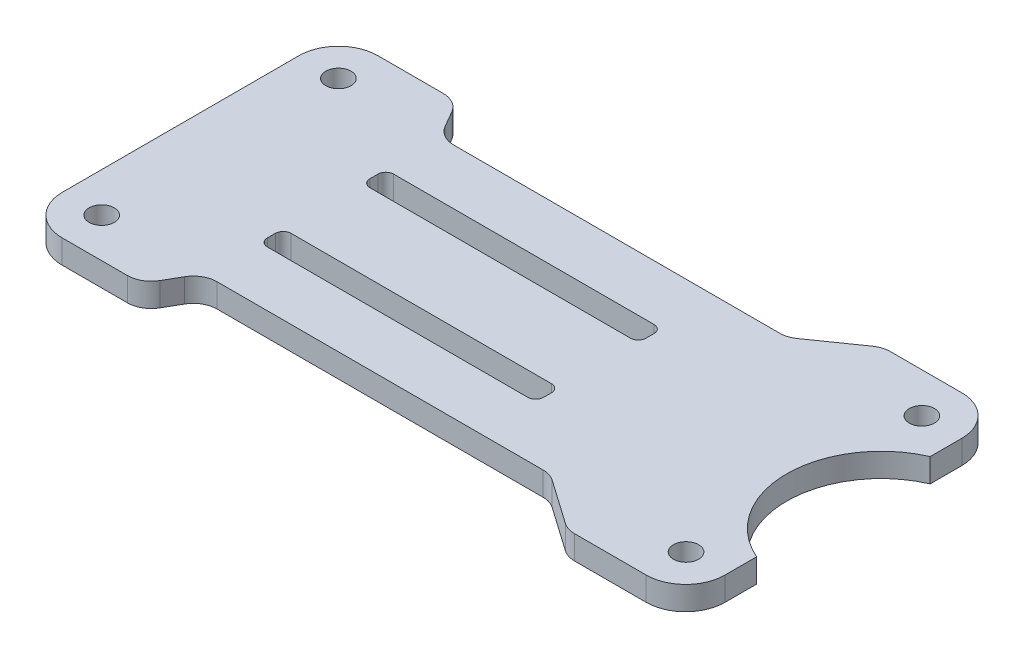
SolidWorks part; units mm, degrees
ref_plane "Front Plane" through (0, 0, 0) normal (0, 0, 1) x (1, 0, 0)
ref_plane "Top Plane" through (0, 0, 0) normal (0, 1, 0) x (1, 0, 0)
ref_plane "Right Plane" through (0, 0, 0) normal (1, 0, 0) x (0, 0, -1)
sketch "Sketch1" plane through (0, 53, 0) normal (0, 1, 0) x (1, 0, 0)
  line L8 (42, -14.9441) -> (42, 14.9441) construction
  line L9 (-37, 20) -> (37, 20)
  line L10 (-42, 15) -> (-42, -15)
  line L11 (-37, -20) -> (37, -20)
  line L12 (42, 15) -> (42, -15)
  line L13 (-42, 15) -> (-42, -15) construction
  line L14 (-3.2304, -20) -> (4.6447, -20) construction
  line L15 (-35.7279, 20) -> (-37, 20) construction
  arc A12 (37, 20) -> (42, 15) centre (37, 15) cw
  arc A13 (37, -20) -> (42, -15) centre (37, -15) ccw
  arc A14 (-42, -15) -> (-37, -20) centre (-37, -15) ccw
  arc A15 (-37, 20) -> (-42, 15) centre (-37, 15) ccw
  circle A17 centre (37, 14.9441) radius 1.6 construction
  circle A18 centre (37, 14.9441) radius 1.6
  circle A19 centre (37, -14.9441) radius 1.6 construction
  circle A20 centre (37, -14.9441) radius 1.6
  circle A21 centre (-37, -15) radius 1.6 construction
  circle A22 centre (-37, -15) radius 1.6
  circle A23 centre (-37, 15) radius 1.6 construction
  circle A24 centre (-37, 15) radius 1.6
  dimension "D1" = 0
  dimension "D5" = 5
  dimension "D2" = 0
  dimension "D3" = 0
  dimension "D4" = 0
extrude "Boss-Extrude1" add sketch "Sketch1" along normal blind 3
sketch "Sketch2" plane through (0, 56, 0) normal (0, 1, 0) x (1, 0, 0)
  line L0 (-27, 20) -> (-24.1132, 15)
  line L1 (37, 20) -> (-37, 20) construction
  line L2 (-24.1132, 15) -> (19.8593, 15)
  line L3 (19.8593, 15) -> (27, 20)
  line L4 (-27, 20) -> (27, 20)
  line L5 (42, -15) -> (42, 15) construction
  line L6 (-42, 15) -> (-42, -15) construction
  line L7 (-42, 0) -> (42, 0) construction
  line L8 (-27, -20) -> (27, -20)
  line L9 (19.8593, -15) -> (27, -20)
  line L10 (-24.1132, -15) -> (19.8593, -15)
  line L11 (-27, -20) -> (-24.1132, -15)
  line L12 (42, 11) -> (42, -11)
  arc A0 (42, 11) -> (42, -11) centre (46.7958, 0) ccw
  dimension "D8" = 12
  dimension "D1" = 35
  dimension "D2" = 60
  dimension "D3" = 5
  dimension "D4" = 15
  dimension "D5" = 15
  dimension "D6" = 11
  dimension "D7" = 11
extrude "Cut-Extrude1" cut sketch "Sketch2" against normal up to surface (3 mm away) up to face at (-37, 53, 16.6)
fillet "Fillet1" radius 3 8 edges at (19.8593, 54.5, -15) (27, 54.5, -20) (-27, 54.5, -20) (-24.1132, 54.5, -15) (-27, 54.5, 20) (-24.1132, 54.5, 15) (19.8593, 54.5, 15) (27, 54.5, 20)
sketch "Sketch3" plane through (0, 56, 0) normal (0, 1, 0) x (1, 0, 0)
  line L0 (-42, 0) -> (42, 0) construction
  line L1 (-23, 8) -> (10, 8)
  line L2 (-24, 7) -> (-24, 6)
  line L3 (-23, 5) -> (10, 5)
  line L4 (11, 7) -> (11, 6)
  line L9 (-42, 15) -> (-42, -15) construction
  line L10 (42, 0) -> (42, 11) construction
  line L11 (0, 0) -> (0, 22.1212) construction
  line L12 (11, -7) -> (11, -6)
  line L13 (-23, -5) -> (10, -5)
  line L14 (-24, -7) -> (-24, -6)
  line L15 (-23, -8) -> (10, -8)
  arc A0 (-23, -5) -> (-24, -6) centre (-23, -6) ccw
  arc A1 (-24, -7) -> (-23, -8) centre (-23, -7) ccw
  arc A2 (11, -7) -> (10, -8) centre (10, -7) cw
  arc A3 (11, -6) -> (10, -5) centre (10, -6) ccw
  arc A4 (10, 8) -> (11, 7) centre (10, 7) cw
  arc A5 (10, 5) -> (11, 6) centre (10, 6) ccw
  arc A6 (-24, 6) -> (-23, 5) centre (-23, 6) ccw
  arc A7 (-23, 8) -> (-24, 7) centre (-23, 7) ccw
  point P14 (0, 0)
  point P15 (-24, 6.5)
  point P22 (-24, -5)
  point P25 (-24, -8)
  point P28 (11, -8)
  point P31 (11, -5)
  point P34 (11, 8)
  point P37 (11, 5)
  point P40 (-24, 5)
  point P43 (-24, 8)
  dimension "D5" = 1
  dimension "D1" = 3
  dimension "D2" = 35
  dimension "D3" = 24
  dimension "D4" = 5
extrude "Cut-Extrude2" cut sketch "Sketch3" against normal through all
